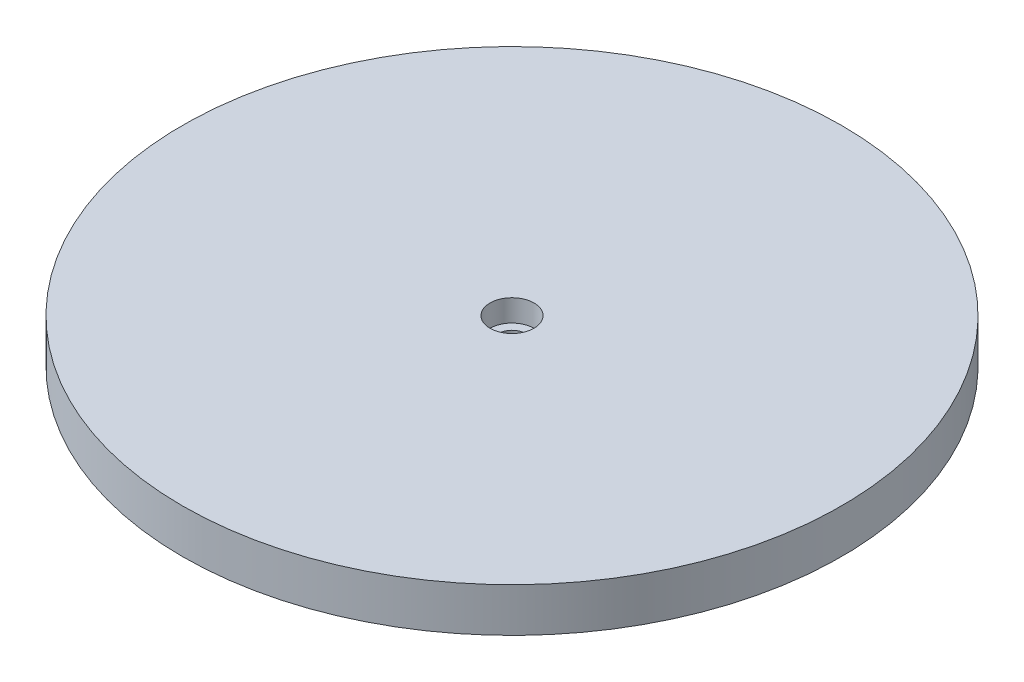
SolidWorks part; units mm, degrees
ref_plane "前视基准面" through (0, 0, 0) normal (0, 0, 1) x (1, 0, 0)
ref_plane "上视基准面" through (0, 0, 0) normal (0, 1, 0) x (1, 0, 0)
ref_plane "右视基准面" through (0, 0, 0) normal (1, 0, 0) x (0, 0, -1)
other "Configuration Table"
sketch "草图1" plane through (0, 0, 0) normal (0, 1, 0) x (1, 0, 0)
  circle A0 centre (0, 0) radius 2.5
  circle A1 centre (0, 0) radius 15
  dimension "D3" = 5
  dimension "D1" = 30
extrude "凸台-拉伸1" add sketch "草图1" along normal blind 2 contours A1
sketch "草图2" plane through (0, 2, 0) normal (0, 1, 0) x (1, 0, 0)
  circle A0 centre (0, 0) radius 1
  circle A1 centre (0, 0) radius 0.6
  dimension "D1" = 1.2
  dimension "D2" = 2
extrude "切除-拉伸1" cut sketch "草图2" against normal through all contours A1
extrude "切除-拉伸2" cut sketch "草图2<3>" against normal blind 1 contours A0
sketch "草图2<3>" plane through (0, 2, 0) normal (0, 1, 0) x (1, 0, 0) same geometry as "草图2"
